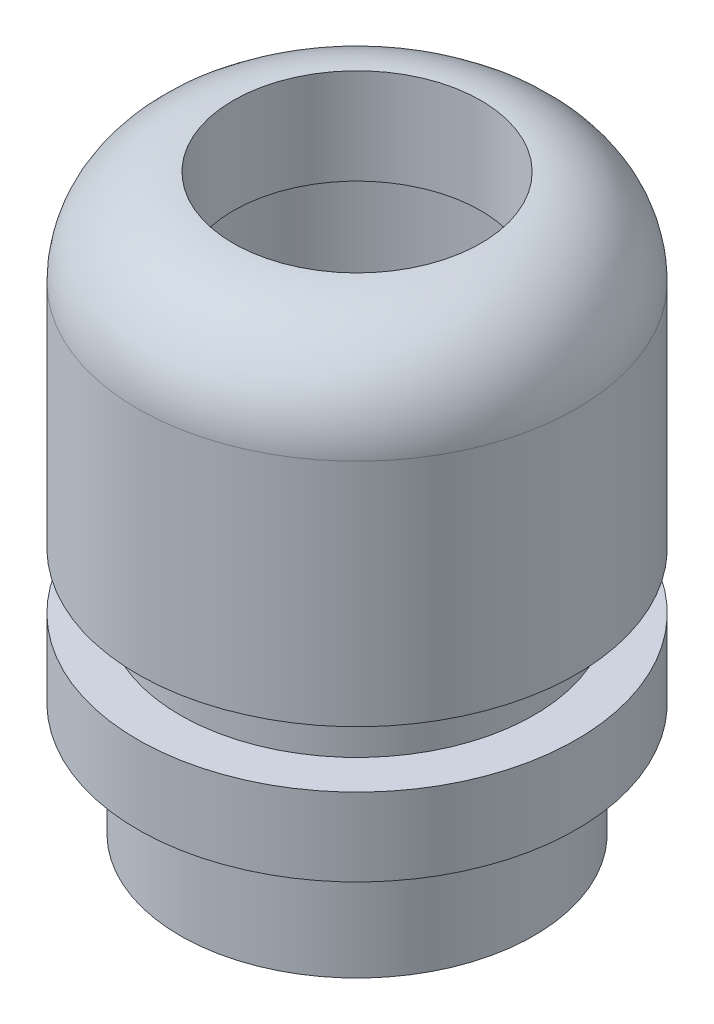
SolidWorks part; units mm, degrees
material "Cremefarbiger Kunstoff"
ref_plane "Vorne" through (0, 0, 0) normal (0, 0, 1) x (1, 0, 0)
ref_plane "Oben" through (0, 0, 0) normal (0, 1, 0) x (1, 0, 0)
ref_plane "Rechts" through (0, 0, 0) normal (1, 0, 0) x (0, 0, -1)
sketch "Skizze2" plane through (0, 0, 0) normal (0, 0, 1) x (1, 0, 0)
  line L0 (0, 275.1751) -> (0, -275.1751) construction
  line L1 (8.75, 20.25) -> (11.5, 20.25)
  line L2 (11.5, 20.25) -> (11.5, -13.5)
  line L3 (11.5, -13.5) -> (12.5, -13.5)
  line L4 (12.5, -13.5) -> (12.5, -5.5)
  line L5 (12.5, -5.5) -> (15.5, -5.5)
  line L6 (15.5, -5.5) -> (15.5, 0)
  line L7 (15.5, 0) -> (12.5, 0)
  line L8 (12.5, 0) -> (12.5, 4)
  line L9 (12.5, 4) -> (15.5, 4)
  line L10 (15.5, 4) -> (15.5, 20.25)
  line L11 (8.75, 27) -> (8.75, 20.25)
  line L12 (11.5, 20.25) -> (15.5, 20.25) construction
  arc A0 (15.5, 20.25) -> (8.75, 27) centre (8.75, 20.25) ccw
  dimension "D1" = 23
  dimension "D2" = 1
  dimension "D4" = 4
  dimension "D5" = 17.5
  dimension "D6" = 5.5
  dimension "D7" = 8
  dimension "D8" = 4
  dimension "D9" = 40.5
revolve "Rotation1" add sketch "Skizze2" angle 360 about L0
other "APunkt1" parameters "Durchmesser"=17.5, "Stumpflänge"=0
ref_axis "Achse1" through (0, 30.25, 0) along (0, -1, 0)
other "LPunkt1"
